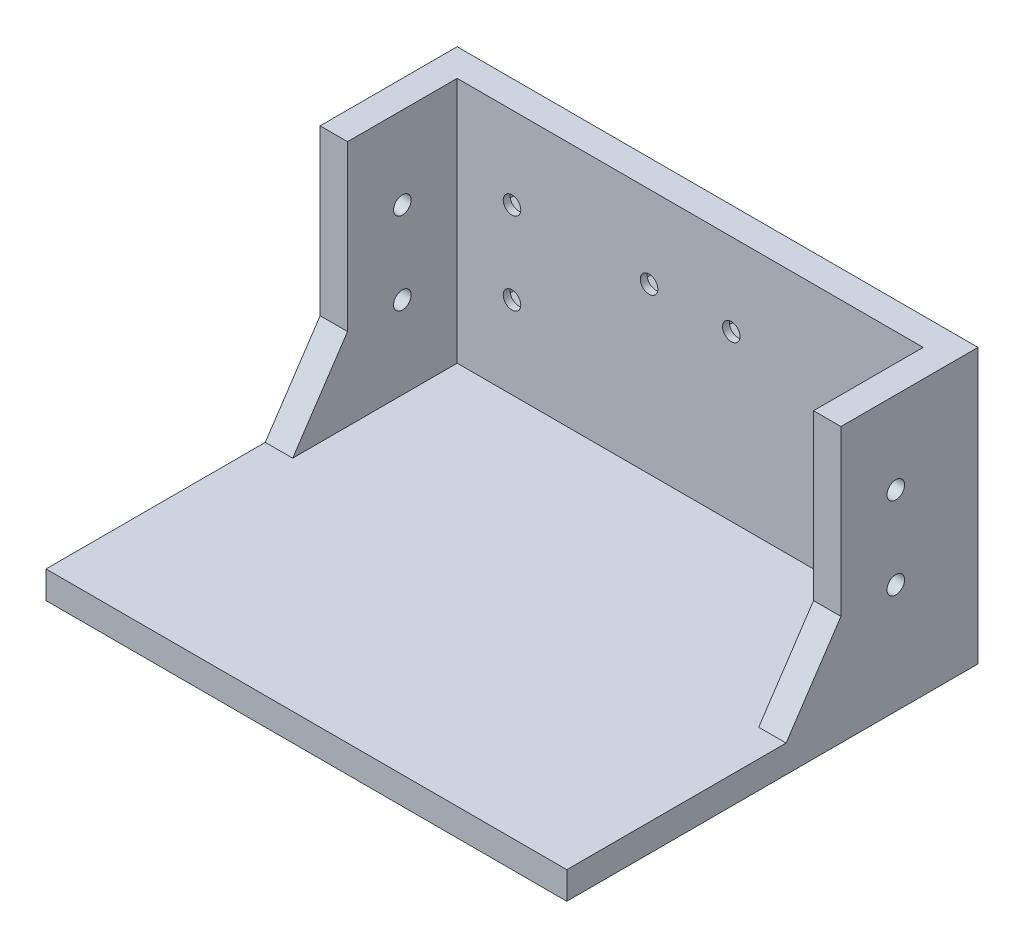
SolidWorks part; units mm, degrees
note: The reader was unsure of these and kept them because the rebuilt part matched: shared geometry of "Sketch7<2>".
ref_plane "Front Plane" through (0, 0, 0) normal (0, 0, 1) x (1, 0, 0)
ref_plane "Top Plane" through (0, 0, 0) normal (0, 1, 0) x (1, 0, 0)
ref_plane "Right Plane" through (0, 0, 0) normal (1, 0, 0) x (0, 0, -1)
sketch "Sketch1" plane through (0, 0, 0) normal (0, 1, 0) x (1, 0, 0)
  line L1 (-47.5, -37.5) -> (47.5, -37.5)
  line L2 (-47.5, -37.5) -> (-47.5, 37.5)
  line L3 (-47.5, 37.5) -> (47.5, 37.5)
  line L4 (47.5, -37.5) -> (47.5, 37.5)
  line L5 (-47.5, -37.5) -> (47.5, 37.5) construction
  line L6 (-47.5, 37.5) -> (47.5, -37.5) construction
  point P0 (0, 0)
  dimension "D1" = 75
  dimension "D2" = 95
extrude "Boss-Extrude1" add sketch "Sketch1" along normal blind 5
sketch "Sketch4" plane through (0, 5, 0) normal (0, 1, 0) x (1, 0, 0)
  line L1 (-47.5, 37.5) -> (-42.5, 37.5)
  line L2 (-47.5, 37.5) -> (-47.5, 12.5)
  line L3 (-47.5, 12.5) -> (-42.5, 12.5)
  line L4 (-42.5, 32.5) -> (-42.5, 12.5)
  line L5 (47.5, 37.5) -> (42.5, 37.5)
  line L6 (47.5, 37.5) -> (47.5, 12.5)
  line L7 (47.5, 12.5) -> (42.5, 12.5)
  line L8 (42.5, 32.5) -> (42.5, 12.5)
  line L9 (-42.5, 37.5) -> (42.5, 37.5)
  line L11 (-42.5, 32.5) -> (42.5, 32.5)
  dimension "D1" = 5
  dimension "D2" = 5
  dimension "D3" = 25
  dimension "D4" = 25
  dimension "D5" = 5
extrude "Boss-Extrude4" add sketch "Sketch4" along normal blind 45
sketch "Sketch5" plane through (-42.5, 0, 0) normal (1, 0, 0) x (0, 0, -1)
  line L0 (22.5, 5) -> (22.5, 20) construction
  line L1 (12.5, 5) -> (32.5, 5) construction
  line L2 (22.5, 20) -> (22.5, 35) construction
  circle A0 centre (22.5, 35) radius 1.6
  circle A1 centre (22.5, 20) radius 1.6
  dimension "D3" = 3.2
  dimension "D4" = 3.2
  dimension "D1" = 15
  dimension "D2" = 15
extrude "Cut-Extrude1" cut sketch "Sketch5" against normal through all both and the other way through all
sketch "Sketch6" plane through (0, 0, -32.5) normal (0, 0, 1) x (1, 0, 0)
  line L0 (0, 50) -> (0, 25.158) construction
  line L1 (-42.5, 50) -> (42.5, 50) construction
  line L2 (-42.5, 27.5) -> (-32.5, 27.5) construction
  line L3 (-42.5, 50) -> (-42.5, 5) construction
  line L4 (-32.5, 27.5) -> (-32.5, 35) construction
  circle A0 centre (-32.5, 35) radius 1.6
  circle A1 centre (-32.5, 20) radius 1.6
  circle A2 centre (32.5, 20) radius 1.6
  circle A3 centre (32.5, 35) radius 1.6
  dimension "D3" = 3.2
  dimension "D1" = 7.5
  dimension "D2" = 10
extrude "Cut-Extrude2" cut sketch "Sketch6" against normal up to next
sketch "Sketch7" plane through (-47.5, 0, 0) normal (-1, 0, 0) x (0, 0, 1)
  line L0 (-12.5, 5) -> (-2.5, 5)
  line L1 (-12.5, 5) -> (37.5, 5) construction
  line L2 (-12.5, 5) -> (-12.5, 20)
  line L3 (-12.5, 50) -> (-12.5, 5) construction
  line L4 (-12.5, 20) -> (-2.5, 5)
  dimension "D1" = 10
  dimension "D2" = 15
extrude "Boss-Extrude5" add sketch "Sketch7" against normal blind 5
extrude "Boss-Extrude6" add sketch "Sketch7<2>" against normal blind 5 from surface at -90 starting at face at (42.5, 35, -24.1)
sketch "Sketch7<2>" plane through (-47.5, 0, 0) normal (-1, 0, 0) x (0, 0, 1) same geometry as "Sketch7"
sketch "Sketch8" plane through (0, 0, -37.5) normal (0, 0, -1) x (-1, 0, 0)
  circle A0 centre (-7.5, 35) radius 1.6
  circle A1 centre (7.5, 35) radius 1.6
extrude "Cut-Extrude3" cut sketch "Sketch8" against normal up to next
sketch "Sketch9" plane through (0, 0, -37.5) normal (0, 0, -1) x (-1, 0, 0)
  line L1 (-32.5, 38.4352) -> (-35.475, 36.7176)
  line L2 (-35.475, 36.7176) -> (-35.475, 33.2824)
  line L3 (-35.475, 33.2824) -> (-32.5, 31.5648)
  line L4 (-32.5, 31.5648) -> (-29.525, 33.2824)
  line L5 (-29.525, 33.2824) -> (-29.525, 36.7176)
  line L6 (-29.525, 36.7176) -> (-32.5, 38.4352)
  line L7 (-7.5, 38.4352) -> (-10.475, 36.7176)
  line L8 (-10.475, 36.7176) -> (-10.475, 33.2824)
  line L9 (-10.475, 33.2824) -> (-7.5, 31.5648)
  line L10 (-7.5, 31.5648) -> (-4.525, 33.2824)
  line L11 (-4.525, 33.2824) -> (-4.525, 36.7176)
  line L12 (-4.525, 36.7176) -> (-7.5, 38.4352)
  line L13 (7.5, 38.4352) -> (4.525, 36.7176)
  line L14 (4.525, 36.7176) -> (4.525, 33.2824)
  line L15 (4.525, 33.2824) -> (7.5, 31.5648)
  line L16 (7.5, 31.5648) -> (10.475, 33.2824)
  line L17 (10.475, 33.2824) -> (10.475, 36.7176)
  line L18 (10.475, 36.7176) -> (7.5, 38.4352)
  line L19 (32.5, 38.4352) -> (29.525, 36.7176)
  line L20 (29.525, 36.7176) -> (29.525, 33.2824)
  line L21 (29.525, 33.2824) -> (32.5, 31.5648)
  line L22 (32.5, 31.5648) -> (35.475, 33.2824)
  line L23 (35.475, 33.2824) -> (35.475, 36.7176)
  line L24 (35.475, 36.7176) -> (32.5, 38.4352)
  line L25 (32.5, 23.4352) -> (29.525, 21.7176)
  line L26 (29.525, 21.7176) -> (29.525, 18.2824)
  line L27 (29.525, 18.2824) -> (32.5, 16.5648)
  line L28 (32.5, 16.5648) -> (35.475, 18.2824)
  line L29 (35.475, 18.2824) -> (35.475, 21.7176)
  line L30 (35.475, 21.7176) -> (32.5, 23.4352)
  line L31 (-32.5, 23.4352) -> (-35.475, 21.7176)
  line L32 (-35.475, 21.7176) -> (-35.475, 18.2824)
  line L33 (-35.475, 18.2824) -> (-32.5, 16.5648)
  line L34 (-32.5, 16.5648) -> (-29.525, 18.2824)
  line L35 (-29.525, 18.2824) -> (-29.525, 21.7176)
  line L36 (-29.525, 21.7176) -> (-32.5, 23.4352)
  circle A0 centre (-32.5, 35) radius 2.975 construction
  circle A1 centre (-7.5, 35) radius 2.975 construction
  circle A2 centre (7.5, 35) radius 2.975 construction
  circle A3 centre (32.5, 35) radius 2.975 construction
  circle A4 centre (32.5, 20) radius 2.975 construction
  circle A5 centre (-32.5, 20) radius 2.975 construction
  dimension "D1" = 5.95
  dimension "D2" = 5.95
  dimension "D3" = 5.95
  dimension "D4" = 5.95
  dimension "D5" = 5.95
  dimension "D6" = 5.95
extrude "Cut-Extrude4" cut sketch "Sketch9" against normal blind 2.5 from offset 1.25 offset against normal yes
